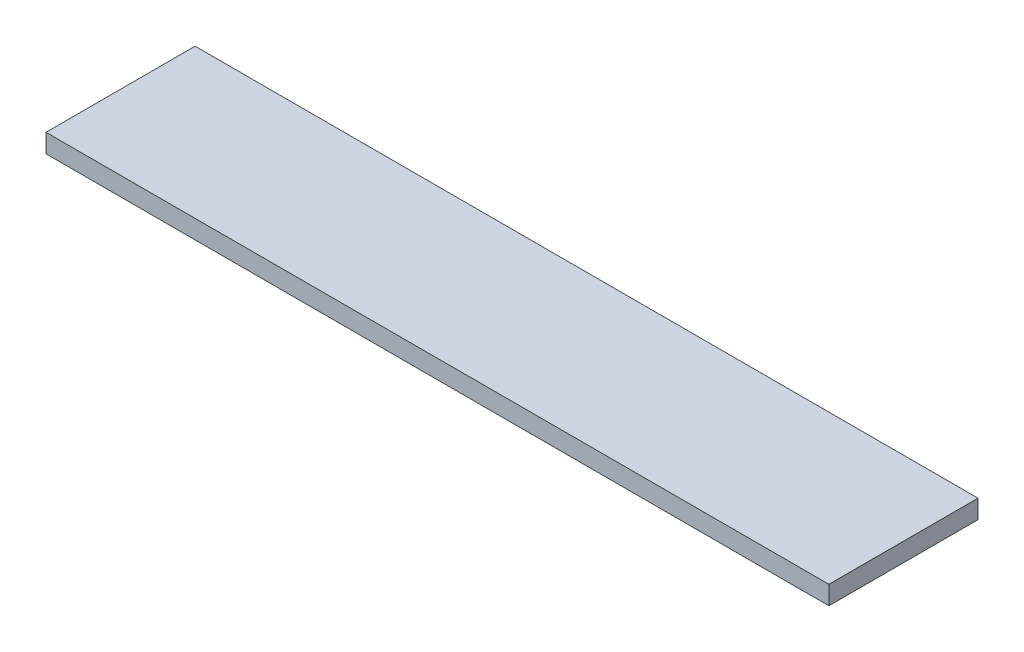
SolidWorks part; units mm, degrees
material "6061-T6 (SS)"
ref_plane "Front" through (0, 0, 0) normal (0, 0, 1) x (1, 0, 0)
ref_plane "Top" through (0, 0, 0) normal (0, 1, 0) x (1, 0, 0)
ref_plane "Right" through (0, 0, 0) normal (1, 0, 0) x (0, 0, -1)
sketch "Sketch1" plane through (0, 0, 0) normal (0, 1, 0) x (1, 0, 0)
  line L0 (266.7, 0) -> (266.7, 19.05) construction
  line L1 (0, 0) -> (266.7, 0)
  line L2 (0, 0) -> (0, 50.8)
  line L3 (0, 50.8) -> (266.7, 50.8)
  line L4 (266.7, 0) -> (266.7, 50.8)
  dimension "D1" = 50.8
extrude "Boss-Extrude1" add sketch "Sketch1" along normal blind 6.35
